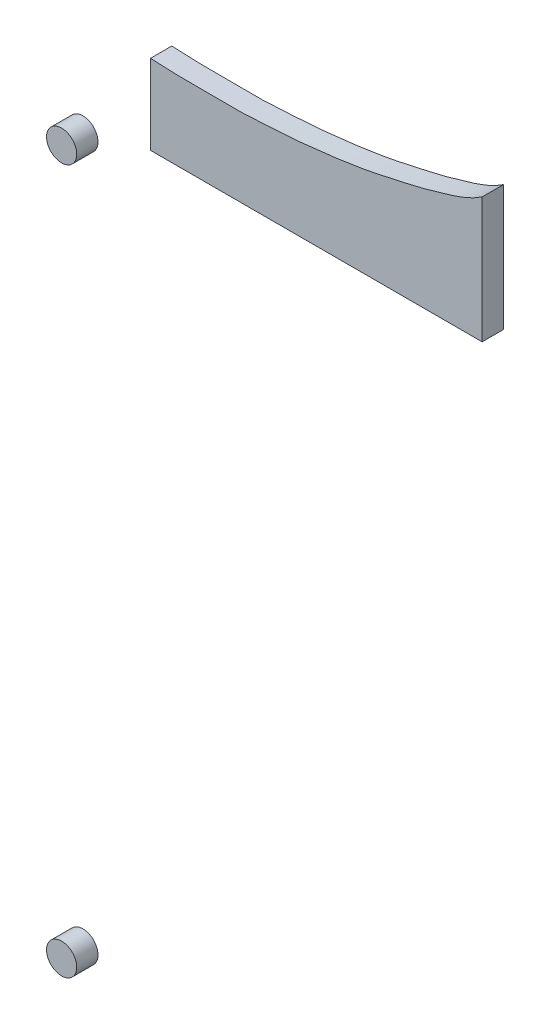
SolidWorks part; units mm, degrees
material "AISI 4340 Steel, annealed"
ref_plane "X-Y Datum" through (0, 0, 0) normal (0, 0, 1) x (1, 0, 0)
ref_plane "X-Z Datum" through (0, 0, 0) normal (0, 1, 0) x (1, 0, 0)
ref_plane "Y-Z Datum" through (0, 0, 0) normal (1, 0, 0) x (0, 0, -1)
sketch3d "3DSketch1"
  line L0 (-464.25, 116.5, 0) -> (-464.25, 118.5, 0)
  line L14 (0, 118.5, 0) -> (-490, 118.5, 0) construction
  line L20 (-477.5, 7.5, -1) -> (-477.5, 7.5, 0) construction
  line L21 (-477.5, 112.5, -1) -> (-477.5, 112.5, 0) construction
  line L25 (-490, 141.4598, 0) -> (-464.25, 141.4598, 0)
  line L26 (-464.25, 118.5, 0) -> (-464.25, 141.4598, 0)
  line L27 (-490, 1.5, 0) -> (-497.05, 1.5, 0)
  line L29 (-490, 141.4598, 0) -> (-497.05, 141.4598, 0)
  line L30 (-497.05, 1.5, 0) -> (-497.05, 141.4598, 0)
  circle A0 centre (-477.5, 7.5, 0) radius 2.25
  circle A1 centre (-477.5, 112.5, 0) radius 2.25
  point P24 (-477.5, 7.5, 2.25)
  point P29 (-477.5, 112.5, 2.25)
  dimension "D1" = 4.5
  dimension "D2" = 4.5
extrude "Boss-Extrude1" add sketch "3DSketch1" along a picked direction on the side against the normal blind 3.175
sketch "Sketch1" plane through (-464.25, 0, 0) normal (1, 0, 0) x (0, 0, -1)
  line L4 (-3.175, 141.4598) -> (-3.175, 118.5)
  line L5 (-3.175, 118.5) -> (0, 118.5)
  line L6 (0, 118.5) -> (0, 141.4598)
  line L7 (0, 141.4598) -> (-3.175, 141.4598)
  line L8 (-3.175, 141.4598) -> (-3.175, 118.5)
  line L9 (-3.175, 118.5) -> (0, 118.5)
  line L10 (0, 118.5) -> (0, 141.4598)
  line L11 (0, 141.4598) -> (-3.175, 141.4598)
  dimension "D1" = 0
extrude "Boss-Extrude2" add sketch "Sketch1" along normal blind 49.4627
sketch "Sketch2" plane through (0, 0, 0) normal (0, 0, -1) x (-1, 0, 0)
  line L0 (414.7873, 118.5) -> (414.7873, 141.4598) construction
  line L3 (490, 141.4598) -> (414.7873, 141.4598)
  line L4 (414.7873, 141.4598) -> (414.7873, 137.2209)
  line L6 (497.05, 1.5) -> (497.05, 141.4598) construction
  line L7 (497.05, 141.4598) -> (497.05, 133.8831)
  line L8 (497.05, 141.4598) -> (490, 141.4598)
  spline S0 degree 3 poles (414.7873, 137.2209) (416.8034, 135.8399) (420.1482, 134.8961) (424.5144, 133.6412) (427.7532, 132.9835) (431.9064, 132.0151) (436.7759, 131.2916) (441.4694, 130.7599) (445.2449, 130.46) (448.1204, 130.3502) (450.4684, 130.1686) (452.2762, 130.2006) (453.6258, 130.1855) (455.2858, 130.2053) (456.8262, 130.2055) (458.2931, 130.2051) (468.7385, 130.2697) (478.8241, 131.8313) (488.0151, 135.3284) knots 0 0 0 0 0.09726 0.137718 0.18266 0.229818 0.308935 0.380085 0.419482 0.460956 0.495635 0.513941 0.533517 0.549828 0.58059 0.595367 0.608726 1 1 1 1
  spline S1 degree 3 poles (488.0151, 135.3284) (490.915, 134.3518) (493.9635, 133.6388) (497.05, 133.8831) knots 0 0 0 0 1 1 1 1
extrude "Cut-Extrude1" cut sketch "Sketch2" against normal blind 5.08
